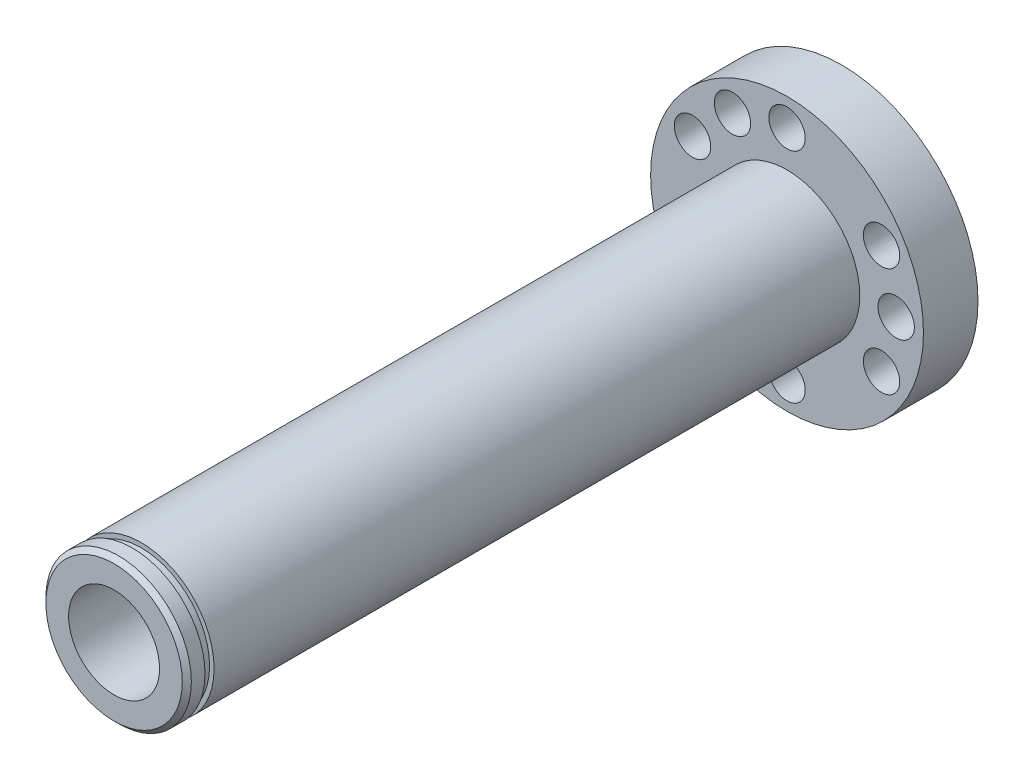
SolidWorks part; units mm, degrees
ref_plane "前视基准面" through (0, 0, 0) normal (0, 0, 1) x (1, 0, 0)
ref_plane "上视基准面" through (0, 0, 0) normal (0, 1, 0) x (1, 0, 0)
ref_plane "右视基准面" through (0, 0, 0) normal (1, 0, 0) x (0, 0, -1)
sketch "草图1" plane through (0, 0, 0) normal (0, 0, 1) x (1, 0, 0)
  circle A0 centre (0, 0) radius 15
  circle A2 centre (0, 12) radius 2
  circle A3 centre (10.3923, 6) radius 2
  circle A4 centre (10.3923, -6) radius 2
  circle A5 centre (0, -12) radius 2
  circle A6 centre (-10.3923, -6) radius 2
  circle A7 centre (-10.3923, 6) radius 2
  circle A8 centre (-6, 10.3923) radius 2
  circle A9 centre (12, 0) radius 2
  circle A10 centre (-6, -10.3923) radius 2
  circle A11 centre (0, 0) radius 5
  dimension "D1" = 30
  dimension "D2" = 6
  dimension "D4" = 3
extrude "凸台-拉伸1" add sketch "草图1" along normal blind 10
sketch "草图2" plane through (0, 0, 10) normal (0, 0, 1) x (1, 0, 0)
  circle A0 centre (0, 0) radius 8
  circle A1 centre (0, 0) radius 5
extrude "凸台-拉伸2" add sketch "草图2" along normal blind 70
sketch "草图3" plane through (0, 0, 0) normal (0, 1, 0) x (1, 0, 0)
  circle A0 centre (0.6768, -59) radius 2.5
extrude "切除-拉伸1" cut sketch "草图3" against normal blind 10
sketch "草图4" plane through (0, 0, 10) normal (0, 0, 1) x (1, 0, 0)
  circle A0 centre (0, 0) radius 8
  circle A1 centre (0, 0) radius 18.074
extrude "切除-拉伸2" cut sketch "草图4" against normal blind 4
fillet "倒角1" radius 0.5 1 edges at (8, 0, 80) type face fillet profile chamfer first side face at (8, 0, 80) second side face at (0.2205, -7.997, 56.542)
sketch "草图5" plane through (0, 0, 0) normal (0, 1, 0) x (1, 0, 0)
  line L1 (7.5, -78) -> (7.5, -77)
  line L8 (7.5, -77) -> (8, -77)
  line L9 (8, -79.5) -> (8, -6) construction
  line L10 (8, -77) -> (8, -78)
  line L11 (8, -78) -> (7.5, -78)
sketch "草图6" plane through (0, 0, 80) normal (0, 0, 1) x (1, 0, 0)
  circle A0 centre (0, 0) radius 7.5
sweep "切除-扫描2" cut profiles "草图5" path "草图6"
